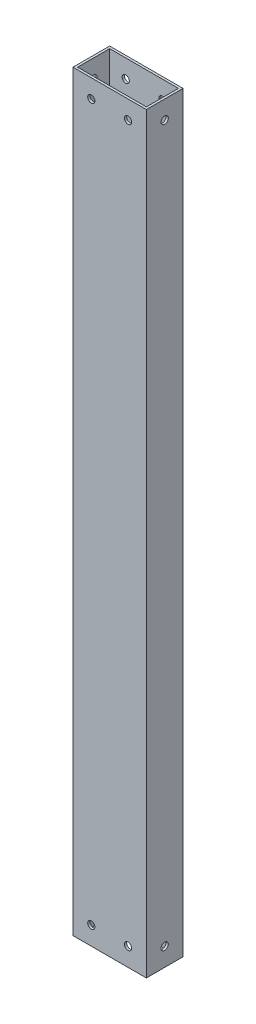
SolidWorks part; units mm, degrees
material "6061-T6 (SS)"
ref_plane "Front Plane" through (0, 0, 0) normal (0, 0, 1) x (1, 0, 0)
ref_plane "Top Plane" through (0, 0, 0) normal (0, 1, 0) x (1, 0, 0)
ref_plane "Right Plane" through (0, 0, 0) normal (1, 0, 0) x (0, 0, -1)
sketch "Sketch1" plane through (0, 0, 0) normal (0, 0, 1) x (1, 0, 0)
  line L1 (-25.4, -260.35) -> (25.4, -260.35)
  line L2 (-25.4, -260.35) -> (-25.4, 260.35)
  line L3 (-25.4, 260.35) -> (25.4, 260.35)
  line L4 (25.4, -260.35) -> (25.4, 260.35)
  line L5 (-25.4, -260.35) -> (25.4, 260.35) construction
  line L6 (-25.4, 260.35) -> (25.4, -260.35) construction
  point P0 (0, 0)
  dimension "D1" = 50.8
  dimension "D2" = 520.7
extrude "Boss-Extrude1" add sketch "Sketch1" along normal mid plane 25.4
shell "Shell1" thickness 1.5875 removed face at (0, -260.35, 0) removed face at (0, 260.35, 0)
sketch "Sketch2" plane through (0, 0, 0) normal (0, 0, 1) x (1, 0, 0)
  line L0 (-25.4, 260.35) -> (-25.4, -260.35) construction
  line L1 (-25.4, -260.35) -> (25.4, -260.35) construction
  line L2 (-25.4, 0) -> (25.4, 0) construction
  line L3 (25.4, -260.35) -> (25.4, 260.35) construction
  circle A0 centre (-12.7, -247.65) radius 2.4892
  circle A1 centre (12.7, -247.65) radius 2.4892
  circle A2 centre (12.7, 247.65) radius 2.4892
  circle A3 centre (-12.7, 247.65) radius 2.4892
  dimension "D1" = 4.9784
  dimension "D3" = 25.4
  dimension "D2" = 12.7
  dimension "D4" = 12.7
extrude "Cut-Extrude1" cut sketch "Sketch2" against normal through all both and the other way through all
sketch "Sketch3" plane through (0, 0, 0) normal (1, 0, 0) x (0, 0, -1)
  line L0 (-12.7, -260.35) -> (12.7, -260.35) construction
  line L1 (-12.7, 260.35) -> (12.7, 260.35) construction
  circle A0 centre (0, -247.65) radius 2.4892
  circle A1 centre (0, 247.65) radius 2.4892
  point P6 (0, -260.35)
  point P9 (0, 260.35)
  dimension "D1" = 4.9784
  dimension "D2" = 12.7
  dimension "D3" = 12.7
extrude "Cut-Extrude2" cut sketch "Sketch3" against normal through all both and the other way through all
